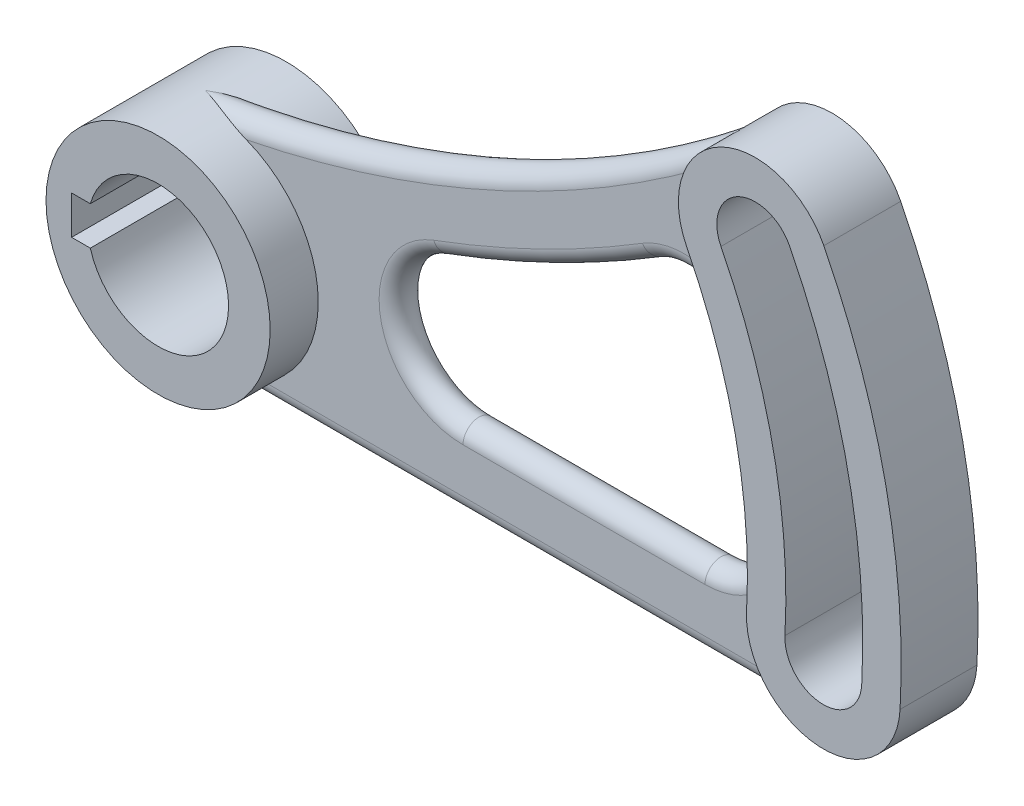
SolidWorks part; units mm, degrees
ref_plane "Front Plane" through (0, 0, 0) normal (0, 0, 1) x (1, 0, 0)
ref_plane "Top Plane" through (0, 0, 0) normal (0, 1, 0) x (1, 0, 0)
ref_plane "Right Plane" through (0, 0, 0) normal (1, 0, 0) x (0, 0, -1)
sketch "Sketch1" plane through (0, 0, 0) normal (0, 0, 1) x (1, 0, 0)
  line L0 (0, 0) -> (11, 0) construction
  line L1 (-10.583, 3) -> (-13.5, 3)
  line L2 (-10.583, -3) -> (-13.5, -3)
  line L3 (-13.5, 3) -> (-13.5, -3)
  arc A0 (-10.583, -3) -> (-10.583, 3) centre (0, 0) ccw
  circle A1 centre (0, 0) radius 17.5
  dimension "D1" = 35
  dimension "D2" = 22
  dimension "D3" = 6
  dimension "D4" = 3
  dimension "D5" = 24.5
  dimension "D6" = 3
extrude "Boss-Extrude1" add sketch "Sketch1" along normal blind 20
ref_plane "Plane1" through (0, 0, 10) normal (0, 0, 1) x (1, 0, 0)
sketch "Sketch2" plane through (0, 0, 10) normal (0, 0, 1) x (1, 0, 0)
  line L0 (0, -17.5) -> (99.8486, -17.5)
  line L1 (0, 0) -> (99.8486, -5.5) construction
  line L2 (0, 0) -> (89.2215, 45.1612) construction
  line L3 (87.8486, -5.5) -> (40.0967, -5.5)
  line L4 (17.5, 10.6103) -> (17.5, -9.1503) construction
  line L5 (29.5, 14.8663) -> (29.5, -5.644) construction
  circle A0 centre (0, 0) radius 17.5 construction
  circle A1 centre (0, 0) radius 100 construction
  arc A2 (87.8668, -4.84) -> (111.8305, -6.16) centre (99.8486, -5.5) ccw
  arc A3 (93.8577, -5.17) -> (105.8396, -5.83) centre (99.8486, -5.5) ccw
  arc A4 (99.928, 50.5805) -> (78.5149, 39.7418) centre (89.2215, 45.1612) ccw
  arc A5 (94.5747, 47.8708) -> (83.8682, 42.4515) centre (89.2215, 45.1612) ccw
  arc A6 (99.928, 50.5805) -> (111.8305, -6.16) centre (0, 0) cw
  arc A7 (78.5149, 39.7418) -> (87.8668, -4.84) centre (0, 0) cw
  arc A8 (93.8577, -5.17) -> (83.8682, 42.4515) centre (0, 0) ccw
  arc A9 (94.5747, 47.8708) -> (105.8396, -5.83) centre (0, 0) cw
  arc A10 (-2.6016, 17.3055) -> (81.6596, 54.4788) centre (-28.6175, 190.3609) ccw
  arc A11 (79.666, 37.9022) -> (36.4117, 15.0321) centre (-28.6175, 190.3609) cw
  arc A12 (40.0967, -5.5) -> (36.4117, 15.0321) centre (40.0967, 5.0967) cw
  arc A13 (-2.6016, 17.3055) -> (0, -17.5) centre (0, 0) cw
  dimension "D1" = 200
  dimension "D2" = 24
  dimension "D3" = 6
  dimension "D5" = 24
  dimension "D6" = 12
  dimension "D7" = 175
  dimension "D9" = 12
  dimension "D4" = 30
  dimension "D8" = 12
  dimension "D10" = 12
extrude "Boss-Extrude2" add sketch "Sketch2" along normal mid plane 5 contours A10 A13 L0 A2 L3 A12 A11 A4 region at (18.6999, 1.3978, 10)
extrude "Boss-Extrude3" add sketch "Sketch2<3>" along normal mid plane 12 contours A4 A7 A2 A6 A5 A9 A3 A8 region at (91.9458, -13.4029, 10)
sketch "Sketch2<3>" plane through (0, 0, 10) normal (0, 0, 1) x (1, 0, 0) same geometry as "Sketch2"
fillet "Fillet1" radius 10 2 edges at (87.8486, -5.5, 10) (79.4816, 37.7714, 10)
fillet "Fillet6" 2 edges at (42.0182, 30.2498, 7.5) (42.0182, 30.2498, 12.5) type full round first side face at (62.7495, 10.8672, 7.5) second side face at (62.7495, 10.8672, 12.5) middle face at (40.7736, 33.071, 10)
fillet "Fillet7" 10 edges at (58.9834, -5.5, 7.5) (29.6667, 3.2248, 7.5) (53.3075, 22.2619, 7.5) (78.2006, 31.9495, 7.5) (85.1423, -2.3641, 7.5) (58.9834, -5.5, 12.5) (29.6667, 3.2248, 12.5) (53.3075, 22.2619, 12.5) (85.1423, -2.3641, 12.5) (78.2006, 31.9495, 12.5) type full round first side face at (62.8545, 10.0097, 7.5) second side face at (62.8545, 10.0097, 12.5) middle face at (84.002, -1.2878, 10) middle face at (77.5097, 30.1277, 10) middle face at (53.1097, 22.6678, 10) middle face at (33.9604, 3.9954, 10) middle face at (58.9834, -5.5, 10)
fillet "Fillet8" 2 edges at (49.9243, -17.5, 7.5) (49.9243, -17.5, 12.5) type full round first side face at (62.0083, 9.8304, 7.5) second side face at (62.0083, 9.8304, 12.5) middle face at (49.9243, -17.5, 10)
